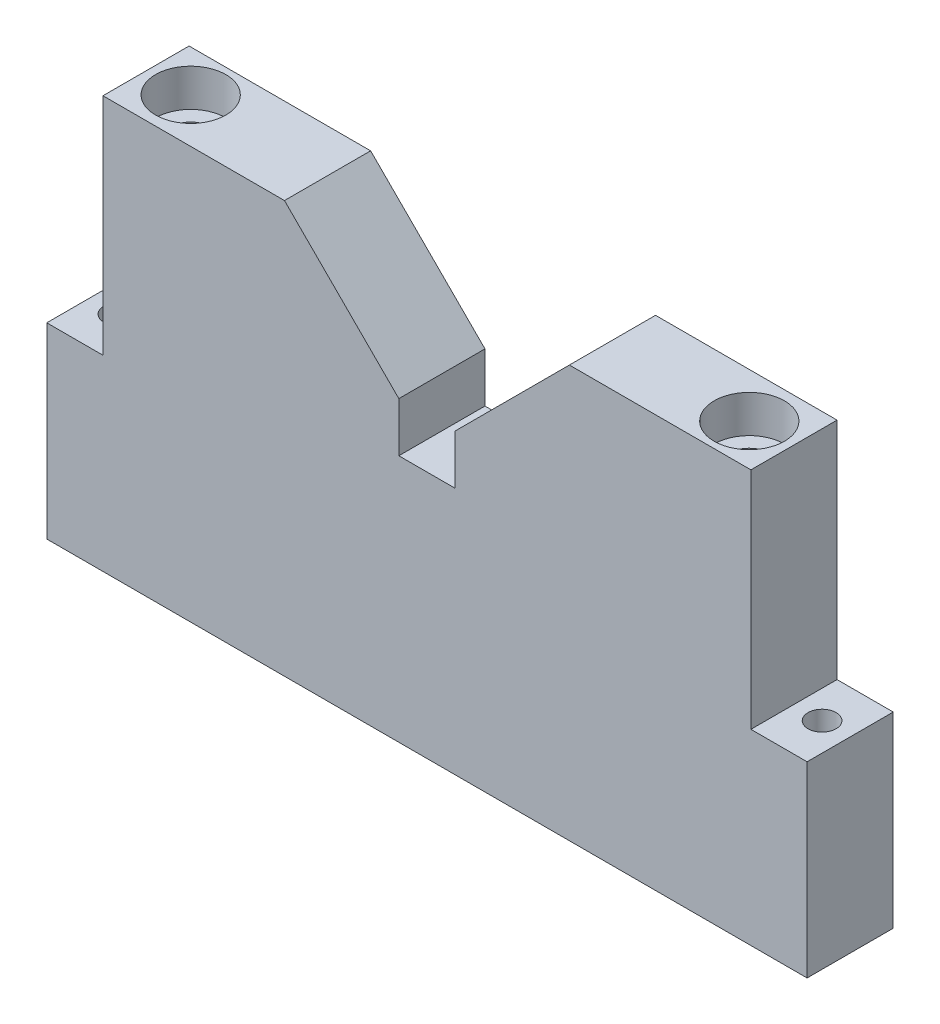
SolidWorks part; units mm, degrees
ref_plane "Спереди" through (0, 0, 0) normal (0, 0, 1) x (1, 0, 0)
ref_plane "Сверху" through (0, 0, 0) normal (0, 1, 0) x (1, 0, 0)
ref_plane "Справа" through (0, 0, 0) normal (1, 0, 0) x (0, 0, -1)
sketch "Эскиз1" plane through (0, 0, 0) normal (0, 0, 1) x (1, 0, 0)
  line L0 (-69.2, -12) -> (-30.4264, -12)
  line L1 (-30.4264, -12) -> (-6, -36.4264)
  line L2 (-6, -36.4264) -> (-6, -47)
  line L3 (-6, -47) -> (6, -47)
  line L4 (6, -47) -> (6, -36.4264)
  line L5 (6, -36.4264) -> (30.4264, -12)
  line L6 (30.4264, -12) -> (69.2, -12)
  line L7 (69.2, -12) -> (69.2, -60)
  line L8 (69.2, -60) -> (-69.2, -60)
  line L9 (-69.2, -60) -> (-69.2, -12)
  circle A0 centre (0, 0) radius 30 construction
  dimension "D1" = 60
  dimension "D3" = 60
  dimension "D2" = 12
  dimension "D4" = 138.4
  dimension "D5" = 12
  dimension "D6" = 35
extrude "Бобышка-Вытянуть1" add sketch "Эскиз1" along normal mid plane 18.4
sketch "Эскиз2" plane through (0, -60, 0) normal (0, -1, 0) x (1, 0, 0)
  line L0 (-81.2, -9.2) -> (81.2, 9.2) construction
  line L1 (-81.2, 9.2) -> (81.2, 9.2)
  line L2 (-81.2, 9.2) -> (-81.2, -9.2)
  line L3 (-81.2, -9.2) -> (81.2, -9.2)
  line L4 (81.2, 9.2) -> (81.2, -9.2)
  line L6 (-69.2, 9.2) -> (69.2, 9.2) construction
  dimension "D1" = 162.4
extrude "Бобышка-Вытянуть2" add sketch "Эскиз2" along normal blind 40
hole_wizard "Цековка для винта с внутренним шестигранником M82" positions "Эскиз12" profile "Эскиз11" counterbore size "M8" standard "ISO" end condition through all
sketch "Эскиз12" plane through (0, -12, 0) normal (0, 1, 0) x (-1, 0, 0)
  line L0 (60, -0.3438) -> (-60, 0.3438) construction
  point P0 (-60, 0.3438)
  point P1 (60, -0.3438)
  dimension "D1" = 120
sketch "Эскиз11" plane through (60, -12, 0.3438) normal (1, 0, 0) x (0, 0, 1)
  line L0 (0, 0) -> (0, 88)
  line L1 (0, 88) -> (4.2, 88)
  line L3 (4.2, 88) -> (4.2, 8)
  line L4 (4.2, 8) -> (7.5, 8)
  line L5 (7.5, 8) -> (7.5, 0)
  line L7 (7.5, 0) -> (0, 0)
  line L11 (0, -6.35) -> (0, 107.95) construction
  dimension "Диаметр сквозного отверстия" = 8.4
  dimension "Глубина сквозного отверстия" = 88
  dimension "Диаметр цековки" = 15
  dimension "Глубина цековки" = 8
hole_wizard "Диаметр отверстия Ø6.0 (6)2" positions "Эскиз14" profile "Эскиз13" hole size "Ø6.0" standard "ISO" end condition through all
sketch "Эскиз14" plane through (0, -60, 0) normal (0, 1, 0) x (-1, 0, 0)
  line L0 (-75.2, 0) -> (75.2, 0) construction
  line L3 (-81.2, -9.2) -> (-81.2, 9.2) construction
  point P0 (-75.2, 0)
  point P1 (75.2, 0)
  dimension "D1" = 6
sketch "Эскиз13" plane through (75.2, -60, 0) normal (1, 0, 0) x (0, 0, 1)
  line L0 (0, 0) -> (0, 40)
  line L1 (0, 40) -> (3, 40)
  line L2 (3, 40) -> (3, 0)
  line L5 (3, 0) -> (0, 0)
  line L11 (0, -6.35) -> (0, 107.95) construction
  dimension "Диаметр сквозного отверстия" = 6
  dimension "Глубина сквозного отверстия" = 40
ref_plane "___mouting_plane_1___" through (21.2132, -21.2132, 0) normal (-0.7071, 0.7071, 0) x (0, 0, 1)
ref_plane "___mouting_plane_2___" through (-21.2132, -21.2132, 0) normal (0.7071, 0.7071, 0) x (0.7071, -0.7071, 0)
equation "\"D\"= 60"
equation "\"D1@Эскиз1\" = \"D\""
equation "\"D2@Эскиз1\" = \"D\"/5"
equation "\"D3@Эскиз1\" = \"D\""
equation "\"D4@Эскиз1\" = 2*\"D\"+\"Диаметр сквозного отверстия@Эскиз11\"+10"
equation "\"D1@Бобышка-Вытянуть1\" = \"Диаметр сквозного отверстия@Эскиз11\"+10"
equation "\"D1@Эскиз12\" = \"D4@Эскиз1\"- \"Диаметр сквозного отверстия@Эскиз11\"-10"
equation "\"D5@Эскиз1\" = \"D1@Эскиз1\"/5"
equation "\"D6@Эскиз1\" = \"D1@Эскиз1\"/2+5"
equation "\"D1@Эскиз2\" = \"D4@Эскиз1\"+\"Диаметр сквозного отверстия@Эскиз13\"*4"
equation "\"D1@Эскиз14\" = \"Диаметр сквозного отверстия@Эскиз13\""
equation "\"___height_cilynder_locator_base___@Бобышка-Вытянуть2\"=40"
